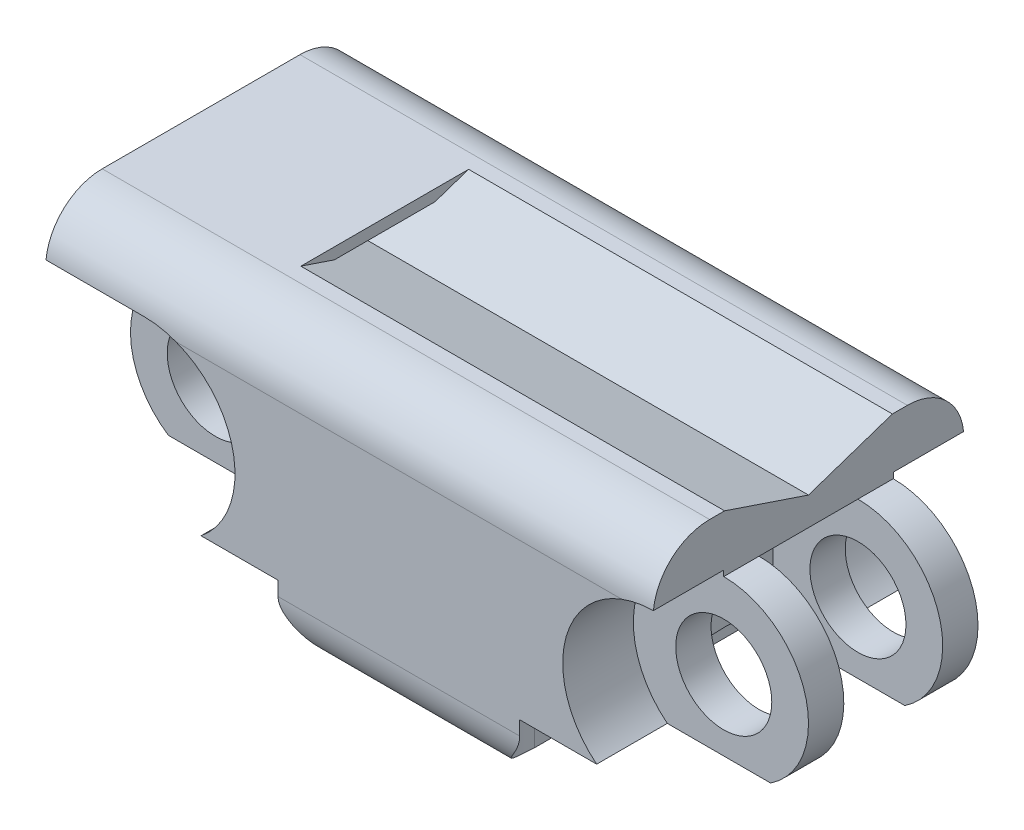
SolidWorks part; units mm, degrees
ref_plane "Front Plane" through (0, 0, 0) normal (0, 0, 1) x (1, 0, 0)
ref_plane "Top Plane" through (0, 0, 0) normal (0, 1, 0) x (1, 0, 0)
ref_plane "Right Plane" through (0, 0, 0) normal (1, 0, 0) x (0, 0, -1)
sketch "Sketch1" plane through (0, 0, 0) normal (0, 0, 1) x (1, 0, 0)
  line L0 (0, 0) -> (18, 0) construction
  line L1 (0, -3) -> (18, -3)
  line L2 (18, 0) -> (18, -3) construction
  line L3 (0, 3) -> (18, 3)
  circle A0 centre (0, 0) radius 1.7
  arc A1 (0, 3) -> (0, -3) centre (0, 0) ccw
  circle A2 centre (18, 0) radius 1.7
  arc A3 (18, -3) -> (18, 3) centre (18, 0) ccw
  dimension "D1" = 3.4
  dimension "D2" = 6
  dimension "D3" = 3.4
  dimension "D4" = 6
  dimension "D5" = 18
extrude "Boss-Extrude1" add sketch "Sketch1" along normal mid plane 6
sketch "Sketch7" plane through (0, 0, 0) normal (1, 0, 0) x (0, 0, -1)
  line L1 (-3.5, -5) -> (3.5, -5)
  line L2 (-5.5, -3) -> (-5.5, 3)
  line L3 (-3.5, 5) -> (3.5, 5)
  line L4 (5.5, -3) -> (5.5, 3)
  line L5 (0, 5) -> (0, -5) construction
  line L6 (-5.5, 0) -> (5.5, 0) construction
  circle A0 centre (0, 0) radius 5 construction
  arc A1 (-3.5, -5) -> (-5.5, -3) centre (-3.5, -3) cw
  arc A2 (3.5, -5) -> (5.5, -3) centre (3.5, -3) ccw
  arc A3 (3.5, 5) -> (5.5, 3) centre (3.5, 3) cw
  arc A4 (-5.5, 3) -> (-3.5, 5) centre (-3.5, 3) cw
  point P8 (-5.5, -5)
  point P14 (5.5, 5)
  point P17 (-5.5, 5)
  dimension "D1" = 10
  dimension "D4" = 2
  dimension "D2" = 11
  dimension "D3" = 10
extrude "Boss-Extrude2" add sketch "Sketch7" along normal blind 18
sketch "Sketch4" plane through (0, 0, 0) normal (0, 0, 1) x (1, 0, 0)
  line L0 (3, 0) -> (3, -3)
  line L1 (0, -3) -> (0, -5.5909)
  line L2 (3, -3) -> (0, -3) construction
  line L3 (15, 0) -> (15, -3)
  line L4 (15, -3) -> (18, -3) construction
  line L6 (0, -5.5909) -> (3, -5.5909)
  line L8 (3, -5.5909) -> (3, -3)
  line L9 (15, -3) -> (15, -5.6135)
  line L10 (15, -5.6135) -> (18, -5.6135)
  line L11 (18, -5.6135) -> (18, -3)
  arc A0 (3, 0) -> (0, -3) centre (0, 0) ccw
  arc A1 (18, -3) -> (15, 0) centre (18, 0) ccw
  arc A2 (0, 3) -> (0, -3) centre (0, 0) ccw construction
  arc A3 (18, -3) -> (18, 3) centre (18, 0) ccw construction
extrude "Cut-Extrude3" cut sketch "Sketch4" against normal mid plane 3.5
sketch "Sketch8" plane through (0, 0, 0) normal (0, 0, 1) x (1, 0, 0)
  circle A0 centre (0, 0) radius 1.7
  circle A1 centre (18, 0) radius 1.7
  arc A2 (0, 1.7) -> (0, -1.7) centre (0, 0) ccw construction
  arc A3 (18, -1.7) -> (18, 1.7) centre (18, 0) ccw construction
extrude "Cut-Extrude4" cut sketch "Sketch8" against normal through all both and the other way through all
sketch "Sketch9" plane through (15, 0, 0) normal (1, 0, 0) x (0, 0, -1)
  line L0 (0, 0) -> (0, -3.0633) construction
  ellipse E0 centre (0, -3.0633) end of major axis (-3, -3.0633) minor radius 1.5
  dimension "D1" = 3
  dimension "D2" = 6
sketch "Sketch10" plane through (0, 0, 0) normal (0, 0, 1) x (1, 0, 0)
  line L0 (15, 0) -> (15, -3.0633) construction
  spline S0 degree 3 poles (15, -1.9369) (10.2696, -2.1091) (5.1849, -1.0948) (0.8816, -3.5488) knots 0 0 0 0 1 1 1 1
sketch "Sketch12" plane through (0, 0, -3) normal (0, 0, -1) x (-1, 0, 0)
  circle A0 centre (-18, 0) radius 3.2
  circle A1 centre (0, 0) radius 3.2
  dimension "D1" = 6.4
extrude "Cut-Extrude6" cut sketch "Sketch12" along normal blind 5
mirror "Mirror1" about plane through (0, 0, 0) normal (0, 0, 1) of "Cut-Extrude6"
sweep "Cut-Sweep1" cut profiles "Sketch9" path "Sketch10"
sketch "Sketch11" plane through (0, 0, 0) normal (1, 0, 0) x (0, 0, -1)
  line L0 (0, 0) -> (0, 4) construction
  line L1 (0, 4) -> (3.5, 5.1786)
  line L2 (0, 4) -> (-3.5, 5.1786)
  line L3 (3.5, 5.1786) -> (3.5, 7.9518)
  line L4 (3.5, 7.9518) -> (-3.5, 7.9518)
  line L5 (-3.5, 7.9518) -> (-3.5, 5.1786)
  line L6 (3.5, 5) -> (-3.5, 5) construction
  dimension "D1" = 7
  dimension "D2" = 1
extrude "Cut-Extrude5" cut sketch "Sketch11" against normal through all both and the other way through all
sketch "Sketch13" plane through (0, 0, 0) normal (0, 1, 0) x (1, 0, 0)
  line L0 (16.3, -3) -> (19.7, -3) construction
  line L1 (16.3, -3) -> (19.7, -3) construction
  line L2 (19.7, 3) -> (16.3, 3) construction
  line L3 (19.7, 3) -> (16.3, 3) construction
  line L4 (18, 3) -> (18, -3) construction
  line L6 (4.1, -5.6) -> (-4.1, -5.6)
  line L7 (6.1, -3.6) -> (6.1, 3.6)
  line L8 (4.1, 5.6) -> (-4.1, 5.6)
  line L9 (-4.1, -5.6) -> (-4.1, 5.6)
  line L10 (0, 5.6) -> (0, -5.6) construction
  line L11 (6.1, 0) -> (-4.1, 0) construction
  line L12 (13.9, -5.6) -> (22.1, -5.6)
  line L13 (11.9, -3.6) -> (11.9, 3.6)
  line L14 (13.9, 5.6) -> (22.1, 5.6)
  line L15 (22.1, -5.6) -> (22.1, 5.6)
  line L16 (18, 5.6) -> (18, -5.6) construction
  line L17 (11.9, 0) -> (22.1, 0) construction
  arc A2 (13.9, -5.6) -> (11.9, -3.6) centre (13.9, -3.6) cw
  arc A3 (11.9, 3.6) -> (13.9, 5.6) centre (13.9, 3.6) cw
  arc A4 (4.1, -5.6) -> (6.1, -3.6) centre (4.1, -3.6) ccw
  arc A5 (6.1, 3.6) -> (4.1, 5.6) centre (4.1, 3.6) ccw
  point P0 (0, 0)
  point P13 (18, 0)
  point P21 (11.9, 5.6)
  point P26 (6.1, 5.6)
  dimension "D1" = 11.2
  dimension "D2" = 10.2
  dimension "D5" = 2
  dimension "D3" = 11.2
  dimension "D4" = 10.2
extrude "Cut-Extrude7" cut sketch "Sketch13" against normal blind 3 from offset 2.5 offset against normal yes
sketch "Sketch14" plane through (0, 5, 0) normal (0, 1, 0) x (1, 0, 0)
  line L0 (18, -3.5) -> (0, -3.5) construction
  line L1 (0, 3.5) -> (3, 3.5)
  line L2 (0, 3.5) -> (0, -3.5)
  line L3 (0, -3.5) -> (3, -3.5)
  line L4 (3, 3.5) -> (3, -3.5)
  dimension "D1" = 3
extrude "Boss-Extrude3" add sketch "Sketch14" against normal blind 0.4
sketch "Sketch15" plane through (0, 0, 0) normal (-1, 0, 0) x (0, 0, 1)
  line L0 (-1.7817, 4.6) -> (1.7817, 4.6) construction
  line L1 (-1.7817, 4.6) -> (1.7817, 4.6)
  line L2 (-1.7817, 4.6) -> (0, 4) construction
  line L3 (-1.7817, 4.6) -> (0, 4)
  line L4 (0, 4) -> (1.7817, 4.6) construction
  line L5 (0, 4) -> (1.7817, 4.6)
  line L8 (3.5, 5) -> (-3.5, 5)
  line L9 (-5.49, 3.2) -> (-3, 3.2)
  line L10 (-3, 3.2) -> (-3, 3)
  line L11 (-3, 3) -> (-1.75, 3)
  line L12 (-1.75, 3) -> (1.75, 3)
  line L13 (1.75, 3) -> (3, 3)
  line L14 (3, 3) -> (3, 3.2)
  line L15 (3, 3.2) -> (5.49, 3.2)
  line L16 (3.5, 5) -> (-3.5, 5)
  line L17 (-5.49, 3.2) -> (-3, 3.2)
  line L18 (-3, 3.2) -> (-3, 3)
  line L19 (-3, 3) -> (-1.75, 3)
  line L20 (-1.75, 3) -> (1.75, 3)
  line L21 (1.75, 3) -> (3, 3)
  line L22 (3, 3) -> (3, 3.2)
  line L23 (3, 3.2) -> (5.49, 3.2)
  arc A2 (5.49, 3.2) -> (3.5, 5) centre (3.5, 3) ccw
  arc A3 (-3.5, 5) -> (-5.49, 3.2) centre (-3.5, 3) ccw
  arc A4 (5.49, 3.2) -> (3.5, 5) centre (3.5, 3) ccw
  arc A5 (-3.5, 5) -> (-5.49, 3.2) centre (-3.5, 3) ccw
  dimension "D1" = 0
extrude "Boss-Extrude4" add sketch "Sketch15" along normal blind 3.5
